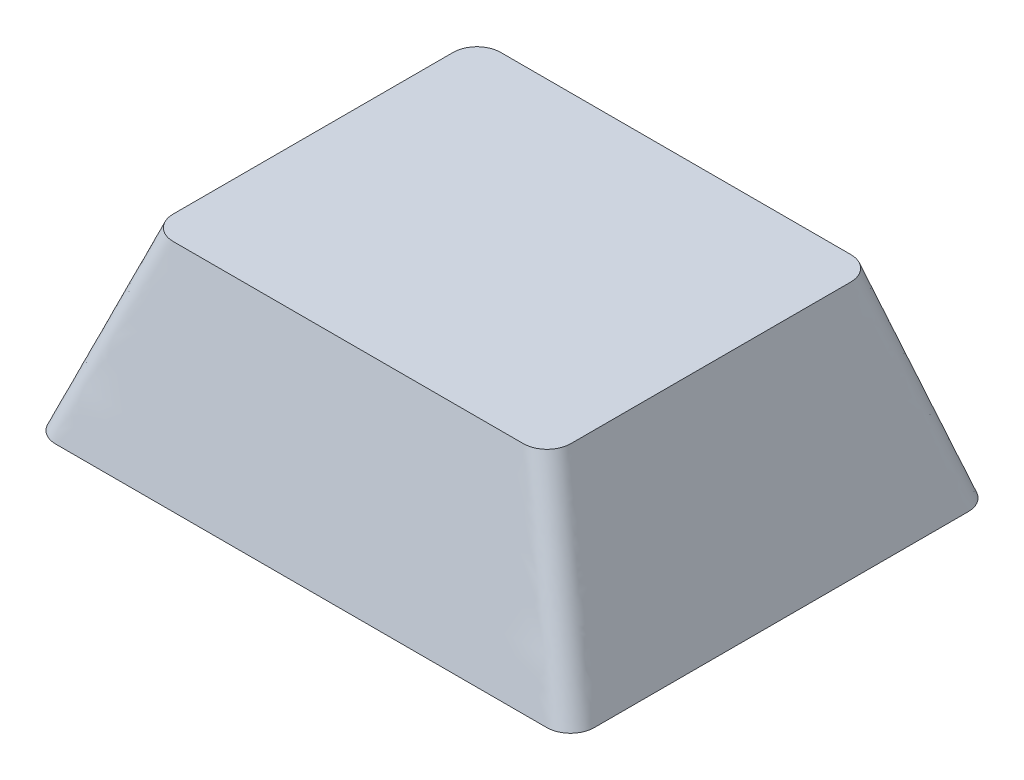
SolidWorks part; units mm, degrees
ref_plane "Alzado" through (0, 0, 0) normal (0, 0, 1) x (1, 0, 0)
ref_plane "Planta" through (0, 0, 0) normal (0, 1, 0) x (1, 0, 0)
ref_plane "Vista lateral" through (0, 0, 0) normal (1, 0, 0) x (0, 0, -1)
sketch "Croquis2" plane through (0, 0, 0) normal (0, 1, 0) x (1, 0, 0)
  line L1 (-10.4902, -9.0043) -> (10.4902, -9.0043)
  line L2 (-11.5062, -7.9883) -> (-11.5062, 7.9883)
  line L3 (-10.4902, 9.0043) -> (10.4902, 9.0043)
  line L4 (11.5062, -7.9883) -> (11.5062, 7.9883)
  arc A0 (-11.5062, 7.9883) -> (-10.4902, 9.0043) centre (-10.4902, 7.9883) cw
  arc A1 (-10.4902, -9.0043) -> (-11.5062, -7.9883) centre (-10.4902, -7.9883) cw
  arc A2 (10.4902, -9.0043) -> (11.5062, -7.9883) centre (10.4902, -7.9883) ccw
  arc A3 (10.4902, 9.0043) -> (11.5062, 7.9883) centre (10.4902, 7.9883) cw
  point P4 (11.5062, 0)
  point P6 (0, 9.0043)
  dimension "D3" = 1.016
  dimension "D1" = 23.0124
  dimension "D2" = 18.0086
ref_plane "Plano1" through (0, 8.001, 0) normal (0, 1, 0) x (1, 0, 0)
sketch "Croquis3" plane through (0, 8.001, 0) normal (0, 1, 0) x (1, 0, 0)
  line L1 (-7.4803, -6.9977) -> (7.4803, -6.9977)
  line L2 (-8.4963, -5.9817) -> (-8.4963, 5.9817)
  line L3 (-7.4803, 6.9977) -> (7.4803, 6.9977)
  line L4 (8.4963, -5.9817) -> (8.4963, 5.9817)
  line L5 (-8.4963, -6.9977) -> (8.4963, 6.9977) construction
  line L6 (-8.4963, 6.9977) -> (8.4963, -6.9977) construction
  arc A0 (7.4803, 6.9977) -> (8.4963, 5.9817) centre (7.4803, 5.9817) cw
  arc A1 (7.4803, -6.9977) -> (8.4963, -5.9817) centre (7.4803, -5.9817) ccw
  arc A2 (-7.4803, -6.9977) -> (-8.4963, -5.9817) centre (-7.4803, -5.9817) cw
  arc A3 (-8.4963, 5.9817) -> (-7.4803, 6.9977) centre (-7.4803, 5.9817) cw
  point P0 (0, 0)
  dimension "D3" = 1.016
  dimension "D1" = 16.9926
  dimension "D2" = 13.9954
loft "Recubrir1" add profiles "Croquis3", "Croquis2" connector at (-7.4803, 8.001, -6.9977) connector at (-10.4902, 0, -9.0043)
